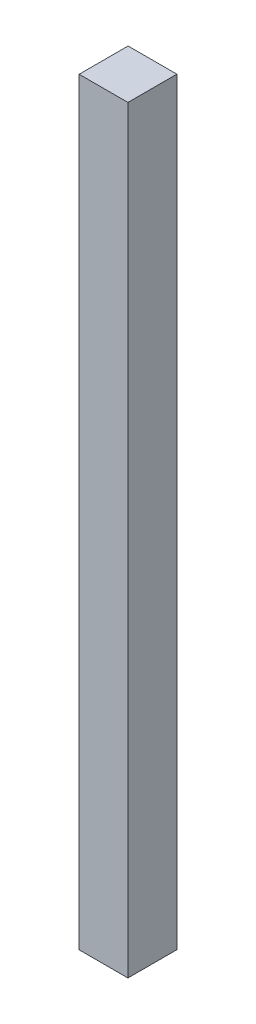
SolidWorks part; units mm, degrees
material "Cedar"
ref_plane "Front" through (0, 0, 0) normal (0, 0, 1) x (1, 0, 0)
ref_plane "Top" through (0, 0, 0) normal (0, 1, 0) x (1, 0, 0)
ref_plane "Right" through (0, 0, 0) normal (1, 0, 0) x (0, 0, -1)
sketch "Sketch1" plane through (0, 0, 0) normal (0, 1, 0) x (1, 0, 0)
  line L1 (-17.399, -17.4625) -> (17.399, -17.4625)
  line L2 (-17.399, -17.4625) -> (-17.399, 17.4625)
  line L3 (-17.399, 17.4625) -> (17.399, 17.4625)
  line L4 (17.399, -17.4625) -> (17.399, 17.4625)
  line L5 (-17.399, -17.4625) -> (17.399, 17.4625) construction
  line L6 (-17.399, 17.4625) -> (17.399, -17.4625) construction
  point P0 (0, 0)
  dimension "D1" = 34.925
  dimension "D2" = 34.798
extrude "Boss-Extrude1" add sketch "Sketch1" along normal blind 541.02 contours L1 L4 L3 L2
